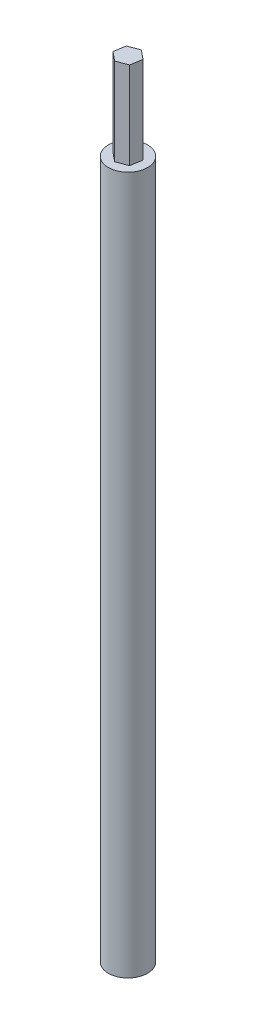
SolidWorks part; units mm, degrees
ref_plane "Front Plane" through (0, 0, 0) normal (0, 0, 1) x (1, 0, 0)
ref_plane "Top Plane" through (0, 0, 0) normal (0, 1, 0) x (1, 0, 0)
ref_plane "Right Plane" through (0, 0, 0) normal (1, 0, 0) x (0, 0, -1)
sketch "Sketch1" plane through (0, 0, 0) normal (0, 1, 0) x (1, 0, 0)
  line L1 (-12.4048, 16.1576) -> (-14.2812, 19.4076)
  line L2 (-14.2812, 19.4076) -> (-18.0339, 19.4076)
  line L3 (-18.0339, 19.4076) -> (-19.9103, 16.1576)
  line L4 (-19.9103, 16.1576) -> (-18.0339, 12.9076)
  line L5 (-18.0339, 12.9076) -> (-14.2812, 12.9076)
  line L6 (-14.2812, 12.9076) -> (-12.4048, 16.1576)
  circle A0 centre (-16.1576, 16.1576) radius 4.5
  circle A1 centre (-16.1576, 16.1576) radius 2.3143
  circle A2 centre (-16.1576, 16.1576) radius 3.25 construction
  dimension "D1" = 9
  dimension "D2" = 6.5
extrude "Boss-Extrude1" add sketch "Sketch1" along normal blind 160 contours A0 L6 L5 L4 L3 L2 L1 | L5 L6 L1 L2 L3 L4 A1 region at (-13.429, 0, -14.5822) region at (-20.5303, 0, -16.1576)
extrude "Cut-Extrude1" cut sketch "Sketch1<3>" along normal blind 5 contours L5 L6 L1 L2 L3 L4 A1 region at (-13.429, 0, -14.5822)
sketch "Sketch1<3>" plane through (0, 0, 0) normal (0, 1, 0) x (1, 0, 0) same geometry as "Sketch1"
sketch "Sketch2" plane through (0, 160, 0) normal (0, 1, 0) x (1, 0, 0)
  line L1 (-14.0922, 14.4629) -> (-13.6573, 17.0989)
  line L2 (-13.6573, 17.0989) -> (-15.7226, 18.7935)
  line L3 (-15.7226, 18.7935) -> (-18.2229, 17.8522)
  line L4 (-18.2229, 17.8522) -> (-18.6578, 15.2163)
  line L5 (-18.6578, 15.2163) -> (-16.5925, 13.5216)
  line L6 (-16.5925, 13.5216) -> (-14.0922, 14.4629)
  circle A0 centre (-16.1576, 16.1576) radius 2.3136 construction
extrude "Boss-Extrude2" add sketch "Sketch2" along normal blind 20
